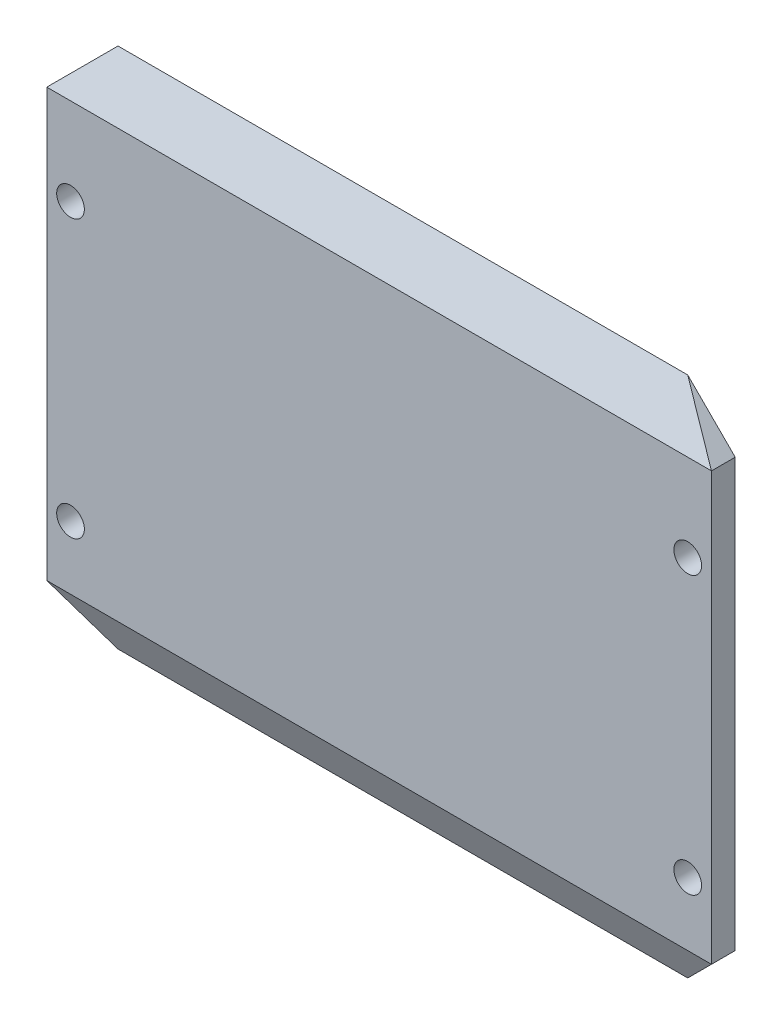
SolidWorks part; units mm, degrees
ref_plane "Front Plane" through (0, 0, 0) normal (0, 0, 1) x (1, 0, 0)
ref_plane "Top Plane" through (0, 0, 0) normal (0, 1, 0) x (1, 0, 0)
ref_plane "Right Plane" through (0, 0, 0) normal (1, 0, 0) x (0, 0, -1)
sketch "Sketch1" plane through (0, 0, 0) normal (0, 0, 1) x (1, 0, 0)
  line L1 (-42, -33) -> (42, -33)
  line L2 (-42, -33) -> (-42, 33)
  line L3 (-42, 33) -> (42, 33)
  line L4 (42, -33) -> (42, 33)
  line L5 (-42, -33) -> (42, 33) construction
  line L6 (-42, 33) -> (42, -33) construction
  point P0 (0, 0)
  dimension "D1" = 84
  dimension "D2" = 66
extrude "Boss-Extrude1" add sketch "Sketch1" along normal blind 3
chamfer "Chamfer2" distance 6 distance2 6 4 edges at (42, -33, 1.5) (-42, -33, 1.5) (-42, 33, 1.5) (42, 33, 1.5)
chamfer "Chamfer4" distance 3 distance2 6 2 edges at (0, -33, 3) (0, 33, 3)
sketch "Sketch2" plane through (0, 0, 3) normal (0, 0, 1) x (1, 0, 0)
  line L0 (-42, -19) -> (42, -19) construction
  line L1 (-42, 27) -> (-42, -27) construction
  line L2 (-42, 16) -> (42, 16) construction
  line L3 (0, 3) -> (0, 13.7383) construction
  line L4 (-36, -33) -> (36, -33) construction
  line L5 (-42, 27) -> (-42, -27) construction
  line L6 (36, 33) -> (-36, 33) construction
  line L7 (42, -27) -> (42, 27) construction
  circle A0 centre (-39, -19) radius 1.75
  circle A1 centre (39, -19) radius 1.75
  circle A2 centre (39, 16) radius 1.75
  circle A3 centre (-39, 16) radius 1.75
  point P4 (0, 0)
  point P5 (0, 0)
  dimension "D1" = 3.5
  dimension "D7" = 3.5
  dimension "D8" = 3.5
  dimension "D2" = 3
  dimension "D3" = 14
  dimension "D4" = 17
  dimension "D5" = 3
  dimension "D6" = 3
extrude "Cut-Extrude1" cut sketch "Sketch2" against normal through all
